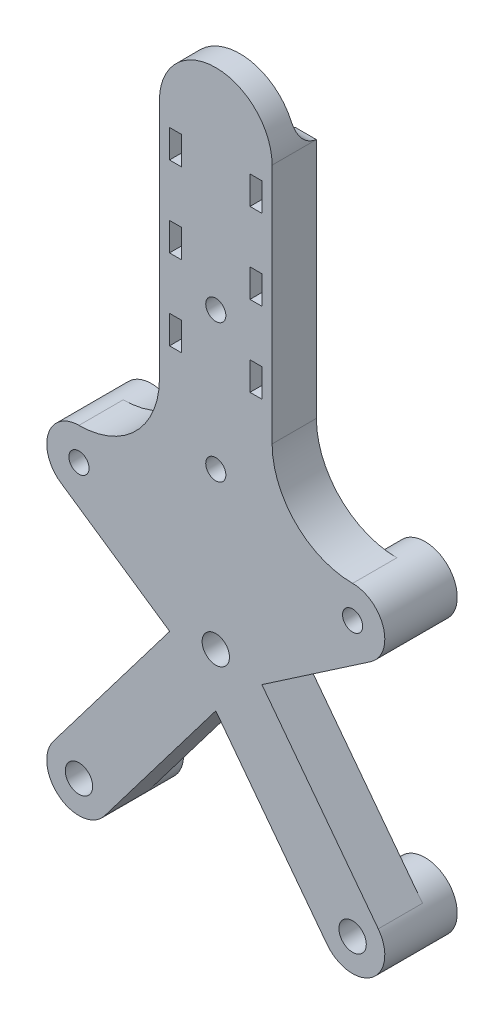
SolidWorks part; units mm, degrees
ref_plane "Front Plane" through (0, 0, 0) normal (0, 0, 1) x (1, 0, 0)
ref_plane "Top Plane" through (0, 0, 0) normal (0, 1, 0) x (1, 0, 0)
ref_plane "Right Plane" through (0, 0, 0) normal (1, 0, 0) x (0, 0, -1)
sketch "Sketch1" plane through (0, 0, 0) normal (0, 0, 1) x (1, 0, 0)
  line L0 (-17, -11.2005) -> (0, 11.2005) construction
  line L1 (-17, -11.2005) -> (-11.9786, -11.2005) construction
  line L2 (-17, -11.2005) -> (-17, -4.5837) construction
  line L3 (-17, 22.7995) -> (17, 22.7995) construction
  line L4 (17, -11.2005) -> (17, -4.5837) construction
  line L5 (0, 11.2005) -> (-17, 22.7995) construction
  line L6 (17, -11.2005) -> (0, 11.2005) construction
  line L7 (0, 11.2005) -> (17, 22.7995) construction
  line L8 (-13.8137, -13.6186) -> (0, 4.5837)
  line L14 (20.1863, -8.7824) -> (5.7296, 10.2674)
  line L16 (-20.1863, -8.7824) -> (-5.7296, 10.2674)
  line L19 (-17, 26.7995) -> (17, 26.7995)
  line L22 (13.8137, -13.6186) -> (0, 4.5837)
  line L25 (5.7296, 10.2674) -> (19.2544, 19.4953)
  line L26 (17, 17.9571) -> (17, 22.7995) construction
  line L27 (-5.7296, 10.2674) -> (-19.2544, 19.4953)
  line L29 (11.9786, -11.2005) -> (17, -11.2005) construction
  line L30 (3.3084, 13.4578) -> (3.1863, 13.6186)
  line L31 (20.1863, -8.7824) -> (3.1863, 13.6186) construction
  line L34 (-3.3084, 13.4578) -> (-3.1863, 13.6186)
  line L35 (-20.1863, -8.7824) -> (-3.1863, 13.6186) construction
  line L36 (0, 26.7995) -> (0, 66.7995) construction
  line L37 (-13.8137, -13.6186) -> (3.1863, 8.7824) construction
  line L38 (7, 26.7995) -> (7, 66.7995)
  line L39 (13.8137, -13.6186) -> (-3.1863, 8.7824) construction
  line L40 (-7, 26.7995) -> (-7, 66.7995)
  line L41 (-17, 17.9571) -> (-17, 22.7995) construction
  arc A0 (-13.8137, -13.6186) -> (-20.1863, -8.7824) centre (-17, -11.2005) cw
  arc A1 (3.3042, 13.4549) -> (3.1863, 13.6186) centre (0, 11.2005) ccw
  arc A2 (-17, -15.2005) -> (-20.1863, -8.7824) centre (-17, -11.2005) cw
  arc A3 (17, -15.2005) -> (20.1863, -8.7824) centre (17, -11.2005) ccw
  arc A4 (-13.8137, -13.6186) -> (-21, -11.2005) centre (-17, -11.2005) cw
  arc A5 (-14.7456, 26.1037) -> (-21, 22.7995) centre (-17, 22.7995) ccw
  arc A6 (-19.2544, 19.4953) -> (-17, 26.7995) centre (-17, 22.7995) cw
  arc A7 (19.2544, 19.4953) -> (17, 26.7995) centre (17, 22.7995) ccw
  arc A8 (21, -11.2005) -> (13.8137, -13.6186) centre (17, -11.2005) cw
  arc A9 (21, 22.7995) -> (14.7456, 26.1037) centre (17, 22.7995) ccw
  arc A10 (3.1863, 13.6186) -> (3.3042, 13.4549) centre (0, 11.2005) cw
  arc A11 (-14.7456, 26.1037) -> (-19.2544, 19.4953) centre (-17, 22.7995) ccw
  arc A12 (20.1863, -8.7824) -> (13.8137, -13.6186) centre (17, -11.2005) cw
  arc A15 (19.2544, 19.4953) -> (14.7456, 26.1037) centre (17, 22.7995) ccw
  circle A16 centre (-17, -11.2005) radius 4
  arc A17 (-3.3042, 13.4549) -> (-3.1863, 13.6186) centre (0, 11.2005) cw
  arc A18 (-3.1863, 13.6186) -> (-3.3042, 13.4549) centre (0, 11.2005) ccw
  circle A19 centre (17, -11.2005) radius 4
  circle A20 centre (17, 22.7995) radius 4
  circle A21 centre (-17, 22.7995) radius 4
  arc A23 (7, 66.7995) -> (-7, 66.7995) centre (0, 66.7995) ccw
  point P0 (17, -11.2005)
  point P1 (-17, -11.2005)
  point P2 (0, 11.2005)
  point P5 (17, 22.7995)
  point P6 (-17, 22.7995)
  dimension "D6" = 40
  dimension "D7" = 34
  dimension "D8" = 34
  dimension "D2" = 4
  dimension "D3" = 4
  dimension "D4" = 7
  dimension "D5" = 7
  dimension "D1" = 2
extrude "Boss-Extrude1" add sketch "Sketch1" along normal blind 3 contours L27 A6 A0 L16 | A21 L27 L16 A16 L8 L22 A19 L14 L25 A20 | A9 L19 A5 | A7 L25 L14 A3 | A8 L22 L8 A0 | L38 A23 L40 L19 | A6 A21 A5 | A9 A20 A7 | A3 A19 A8 | A0 A16 region at (0, 10.5419, 0) region at (-17, -11.2005, 0) region at (17, -11.2005, 0) region at (-17, 22.7995, 0) region at (17, 22.7995, 0) region at (0, 49.5752, 0)
extrude "Boss-Extrude2" add sketch "Sketch1<3>" against normal blind 6 contours A6 A21 A5 | A9 A20 A7 | A3 A19 A8 | A0 A16 region at (-17, -11.2005, 0) region at (17, -11.2005, 0) region at (-17, 22.7995, 0) region at (17, 22.7995, 0)
sketch "Sketch1<3>" plane through (0, 0, 0) normal (0, 0, 1) x (1, 0, 0) same geometry as "Sketch1"
hole_wizard "Tap Drill for M3x0.5 Tap1" positions "Sketch2" profile "Sketch3" hole size "M3x0.5" standard "ANSI Metric"
sketch "Sketch2" plane through (0, 0, -6) normal (0, 0, -1) x (-1, 0, 0)
  point P0 (17, 22.7995)
  point P3 (-17, 22.7995)
sketch "Sketch3" plane through (-17, 22.7995, -6) normal (1, 0, 0) x (0, 1, 0)
  line L0 (0, 0) -> (0, 10.7511)
  line L1 (0, 10.7511) -> (1.25, 10)
  line L2 (1.25, 10) -> (1.25, 0)
  line L5 (1.25, 0) -> (0, 0)
  line L10 (0, 10.7511) -> (-1.25, 10) construction
  line L11 (0, -6.35) -> (0, 107.95) construction
  dimension "Hole Dia." = 2.5
  dimension "Hole Depth" = 10
  dimension "Drill Angle" = 118
hole_wizard "M3 Clearance Hole1" positions "Sketch4" profile "Sketch5" hole size "M3" standard "ANSI Metric"
sketch "Sketch4" plane through (0, 0, -6) normal (0, 0, -1) x (-1, 0, 0)
  point P0 (-17, -11.2005)
  point P3 (17, -11.2005)
sketch "Sketch5" plane through (17, -11.2005, -6) normal (1, 0, 0) x (0, 1, 0)
  line L0 (0, 0) -> (0, 11.0215)
  line L1 (0, 11.0215) -> (1.7, 10)
  line L2 (1.7, 10) -> (1.7, 0)
  line L5 (1.7, 0) -> (0, 0)
  line L10 (0, 11.0215) -> (-1.7, 10) construction
  line L11 (0, -6.35) -> (0, 107.95) construction
  dimension "Hole Dia." = 3.4
  dimension "Hole Depth" = 10
  dimension "Drill Angle" = 118
hole_wizard "M3 Clearance Hole2" positions "Sketch6" profile "Sketch7" hole size "M3" standard "ANSI Metric"
sketch "Sketch6" plane through (0, 0, 3) normal (0, 0, 1) x (1, 0, 0)
  point P0 (0, 11.2005)
sketch "Sketch7" plane through (0, 11.2005, 3) normal (1, 0, 0) x (0, -1, 0)
  line L0 (0, 0) -> (0, 11.0215)
  line L1 (0, 11.0215) -> (1.7, 10)
  line L2 (1.7, 10) -> (1.7, 0)
  line L5 (1.7, 0) -> (0, 0)
  line L10 (0, 11.0215) -> (-1.7, 10) construction
  line L11 (0, -6.35) -> (0, 107.95) construction
  dimension "Hole Dia." = 3.4
  dimension "Hole Depth" = 10
  dimension "Drill Angle" = 118
sketch "Sketch9" plane through (0, 0, 0) normal (0, 0, -1) x (-1, 0, 0)
  line L0 (17, 26.7995) -> (-17, 26.7995) construction
  line L1 (0, 66.7995) -> (4.3656, 66.7995)
  line L2 (0, 66.7995) -> (0, 26.7995)
  line L3 (0, 26.7995) -> (4.3656, 26.7995)
  line L4 (4.3656, 66.7995) -> (4.3656, 26.7995)
  line L6 (0, 66.7995) -> (-4.3656, 66.7995)
  line L7 (0, 66.7995) -> (0, 26.7995)
  line L8 (0, 26.7995) -> (-4.3656, 26.7995)
  line L9 (-4.3656, 66.7995) -> (-4.3656, 26.7995)
  line L10 (-7, 66.7995) -> (7, 66.7995)
  line L11 (-7, 66.7995) -> (-7, 26.7995)
  line L12 (-7, 26.7995) -> (7, 26.7995)
  line L13 (7, 66.7995) -> (7, 26.7995)
  line L20 (0, 4.5837) -> (13.8137, -13.6186)
  line L21 (0, 4.5837) -> (13.8137, -13.6186)
  line L22 (17, 26.7995) -> (7, 26.7995)
  line L23 (7, 26.7995) -> (7, 66.7995)
  line L24 (-7, 66.7995) -> (-7, 26.7995)
  line L25 (-7, 26.7995) -> (-17, 26.7995)
  line L26 (20.1863, -8.7824) -> (5.7296, 10.2674)
  line L27 (20.1863, -8.7824) -> (5.7296, 10.2674)
  line L28 (5.7296, 10.2674) -> (19.2544, 19.4953)
  line L29 (17, 26.7995) -> (7, 26.7995)
  line L30 (7, 26.7995) -> (7, 66.7995)
  line L31 (-7, 66.7995) -> (-7, 26.7995)
  line L32 (-7, 26.7995) -> (-17, 26.7995)
  line L33 (5.7296, 10.2674) -> (19.2544, 19.4953)
  line L37 (-19.2544, 19.4953) -> (-5.7296, 10.2674)
  line L38 (-19.2544, 19.4953) -> (-5.7296, 10.2674)
  line L39 (-5.7296, 10.2674) -> (-20.1863, -8.7824)
  line L40 (-5.7296, 10.2674) -> (-20.1863, -8.7824)
  line L41 (-13.8137, -13.6186) -> (0, 4.5837)
  line L42 (-13.8137, -13.6186) -> (0, 4.5837)
  arc A5 (20.1863, -8.7824) -> (13.8137, -13.6186) centre (17, -11.2005) ccw
  arc A6 (17, 26.7995) -> (19.2544, 19.4953) centre (17, 22.7995) ccw
  arc A7 (7, 66.7995) -> (-7, 66.7995) centre (0, 66.7995) ccw
  arc A8 (-19.2544, 19.4953) -> (-17, 26.7995) centre (-17, 22.7995) ccw
  arc A9 (-13.8137, -13.6186) -> (-20.1863, -8.7824) centre (-17, -11.2005) ccw
  arc A10 (20.1863, -8.7824) -> (13.8137, -13.6186) centre (17, -11.2005) ccw
  arc A11 (17, 26.7995) -> (19.2544, 19.4953) centre (17, 22.7995) ccw
  arc A12 (7, 66.7995) -> (-7, 66.7995) centre (0, 66.7995) ccw
  arc A13 (-19.2544, 19.4953) -> (-17, 26.7995) centre (-17, 22.7995) ccw
  arc A14 (-13.8137, -13.6186) -> (-20.1863, -8.7824) centre (-17, -11.2005) ccw
  circle M19 centre (0, 11.2005) radius 1.7
  arc M25 (13.8137, -13.6186) -> (20.1863, -8.7824) centre (17, -11.2005) cw
  arc M27 (19.2544, 19.4953) -> (17, 26.7995) centre (17, 22.7995) cw
  line M28 (17, 26.7995) -> (7, 26.7995)
  line M29 (7, 26.7995) -> (7, 66.7995)
  line M31 (-7, 66.7995) -> (-7, 26.7995)
  line M32 (-7, 26.7995) -> (-17, 26.7995)
  arc M33 (-17, 26.7995) -> (-19.2544, 19.4953) centre (-17, 22.7995) cw
  arc M35 (-20.1863, -8.7824) -> (-13.8137, -13.6186) centre (-17, -11.2005) cw
  line M37 (20.1863, -8.7824) -> (5.7296, 10.2674)
  line M38 (5.7296, 10.2674) -> (19.2544, 19.4953)
  line M43 (-19.2544, 19.4953) -> (-5.7296, 10.2674)
  line M44 (-5.7296, 10.2674) -> (-20.1863, -8.7824)
  line M46 (-13.8137, -13.6186) -> (0, 4.5837)
  line M47 (0, 4.5837) -> (13.8137, -13.6186)
  dimension "D1" = 4.3656
  dimension "D2" = 4.3656
  dimension "D3" = 0
extrude "Boss-Extrude3" add sketch "Sketch9" along normal blind 2.5 contours L12 L9 L10 M31 | L4 L12 L10 M29 | L12 L3 L8 M32 M33 M35 M25 M27 M28 M47 M46 M44 M43 M38 M37 M19 region at (-5.6828, 46.7995, 0) region at (-2.1828, 26.2282, 0) region at (5.6828, 46.7995, 0)
hole_wizard "Tap Drill for M3x0.5 Tap2" positions "Sketch10" profile "Sketch11" hole size "M3x0.5" standard "ANSI Metric"
sketch "Sketch10" plane through (0, 0, 0) normal (0, 0, -1) x (-1, 0, 0)
  line L0 (0, 26.7995) -> (0, 66.7995) construction
  point P0 (0, 30.5825)
  point P5 (0, 47.7293)
sketch "Sketch11" plane through (0, 30.5825, 0) normal (1, 0, 0) x (0, 1, 0)
  line L0 (0, 0) -> (0, 10.7511)
  line L1 (0, 10.7511) -> (1.25, 10)
  line L2 (1.25, 10) -> (1.25, 0)
  line L5 (1.25, 0) -> (0, 0)
  line L10 (0, 10.7511) -> (-1.25, 10) construction
  line L11 (0, -6.35) -> (0, 107.95) construction
  dimension "Hole Dia." = 2.5
  dimension "Hole Depth" = 10
  dimension "Drill Angle" = 118
sketch "Sketch8" plane through (0, 0, 3) normal (0, 0, 1) x (1, 0, 0)
  line L0 (4.25, 44.4793) -> (5.75, 44.4793)
  line L1 (-5.75, 44.4793) -> (-4.25, 44.4793)
  line L2 (-5.75, 44.4793) -> (-5.75, 40.9793)
  line L3 (-5.75, 40.9793) -> (-4.25, 40.9793)
  line L4 (-4.25, 44.4793) -> (-4.25, 40.9793)
  line L5 (5.75, 44.4793) -> (5.75, 40.9793)
  line L6 (4.25, 44.4793) -> (4.25, 40.9793)
  line L7 (4.25, 40.9793) -> (5.75, 40.9793)
  line L8 (4.25, 54.4793) -> (5.75, 54.4793)
  line L9 (5.75, 54.4793) -> (5.75, 50.9793)
  line L10 (4.25, 54.4793) -> (4.25, 50.9793)
  line L11 (4.25, 50.9793) -> (5.75, 50.9793)
  line L12 (-5.75, 54.4793) -> (-4.25, 54.4793)
  line L13 (-4.25, 54.4793) -> (-4.25, 50.9793)
  line L14 (-5.75, 54.4793) -> (-5.75, 50.9793)
  line L15 (-5.75, 50.9793) -> (-4.25, 50.9793)
  line L16 (-7, 26.7995) -> (-7, 66.7995) construction
  line L17 (-5.75, 64.4793) -> (-4.25, 64.4793)
  line L18 (-4.25, 64.4793) -> (-4.25, 60.9793)
  line L19 (-5.75, 64.4793) -> (-5.75, 60.9793)
  line L20 (-5.75, 60.9793) -> (-4.25, 60.9793)
  line L21 (4.25, 64.4793) -> (5.75, 64.4793)
  line L22 (5.75, 64.4793) -> (5.75, 60.9793)
  line L23 (4.25, 64.4793) -> (4.25, 60.9793)
  line L24 (4.25, 60.9793) -> (5.75, 60.9793)
  dimension "D1" = 1.5
  dimension "D2" = 3.5
  dimension "D5" = 1.25
  dimension "D3" = 2
  dimension "D4" = 3
extrude "Cut-Extrude1" cut sketch "Sketch8" against normal blind 15
fillet "Fillet3" radius 3 2 edges at (5.6828, 66.7995, 0) (-5.6828, 66.7995, 0)
fillet "Fillet4" radius 10 2 edges at (7, 26.7995, 0.25) (-7, 26.7995, 0.25)
